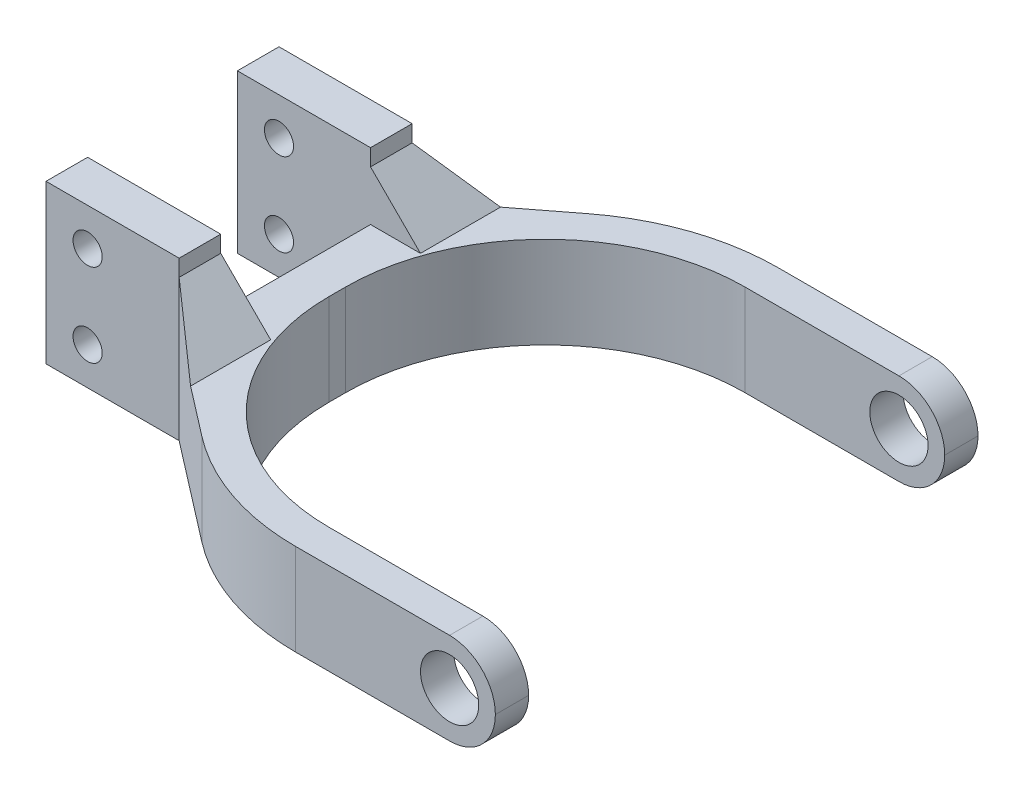
SolidWorks part; units mm, degrees
material "3D printed plastic"
ref_plane "Front Plane" through (0, 0, 0) normal (0, 0, 1) x (1, 0, 0)
ref_plane "Top Plane" through (0, 0, 0) normal (0, 1, 0) x (1, 0, 0)
ref_plane "Right Plane" through (0, 0, 0) normal (1, 0, 0) x (0, 0, -1)
sketch "Sketch1" plane through (0, 0, 0) normal (0, 1, 0) x (1, 0, 0)
  line L0 (-16, 9) -> (-16, 14)
  line L1 (-16, 9) -> (0, 9)
  line L2 (-16, 14) -> (0, 14)
  line L3 (53, -25) -> (29, -25)
  line L4 (0, 9) -> (0, -9)
  line L6 (29, 29) -> (53, 29)
  line L7 (53, 29) -> (53, 25)
  line L8 (53, 25) -> (29, 25)
  line L9 (5, 1) -> (5, -1)
  line L10 (5, 0) -> (0, 0) construction
  line L11 (53, -29) -> (53, -25)
  line L12 (29, -29) -> (53, -29)
  line L14 (-16, -14) -> (0, -14)
  line L15 (-16, -9) -> (0, -9)
  line L16 (-16, -9) -> (-16, -14)
  line L17 (0, 14) -> (11.907, 23.1773)
  line L18 (0, -14) -> (11.907, -23.1773)
  arc A0 (29, 25) -> (5, 1) centre (29, 1) ccw
  arc A1 (29, -25) -> (5, -1) centre (29, -1) cw
  arc A2 (29, 29) -> (11.907, 23.1773) centre (29, 1) ccw
  arc A3 (11.907, -23.1773) -> (29, -29) centre (29, -1) ccw
  point P18 (0, 0)
  point P22 (5, 25)
  point P25 (5, -25)
  dimension "D9" = 24
  dimension "D1" = 18
  dimension "D2" = 5
  dimension "D3" = 16
  dimension "D4" = 16
  dimension "D5" = 5
  dimension "D6" = 50
  dimension "D7" = 4
  dimension "D8" = 48
extrude "Boss-Extrude1" add sketch "Sketch1" along normal mid plane 11
fillet "Fillet1" radius 5.5 4 edges at (53, -5.5, 27) (53, 5.5, 27) (53, -5.5, -27) (53, 5.5, -27)
sketch "Sketch2" plane through (0, 0, 29) normal (0, 0, 1) x (1, 0, 0)
  circle A0 centre (47.5, 0) radius 3.5
  dimension "D1" = 7
extrude "Cut-Extrude1" cut sketch "Sketch2" against normal through all
sketch "Sketch3" plane through (0, 5.5, 0) normal (0, 1, 0) x (1, 0, 0)
  line L0 (-16, -14) -> (0, -14) construction
  line L1 (-16, 14) -> (0, 14)
  line L2 (-16, 14) -> (-16, 9)
  line L3 (-16, 9) -> (0, 9)
  line L4 (0, 14) -> (0, 9)
  line L5 (-16, -9) -> (0, -9)
  line L6 (-16, -9) -> (-16, -14)
  line L7 (-16, -14) -> (0, -14)
  line L8 (0, -9) -> (0, -14)
  line L9 (0, 9) -> (0, -9) construction
extrude "Boss-Extrude2" add sketch "Sketch3" along normal blind 8
sketch "Sketch4" plane through (0, 0, 14) normal (0, 0, 1) x (1, 0, 0)
  line L0 (-11, 9) -> (-11, -1) construction
  line L1 (-11, 4) -> (-16, 4) construction
  line L2 (-16, 13.5) -> (-16, -5.5) construction
  circle A0 centre (-11, 9) radius 1.75
  circle A1 centre (-11, -1) radius 1.75
  dimension "D1" = 3.5
  dimension "D2" = 5
  dimension "D3" = 10
extrude "Cut-Extrude2" cut sketch "Sketch4" against normal through all
chamfer "Chamfer1" distance 6 angle 45 2 edges at (0, 5.5, -11.5) (0, 5.5, 11.5)
